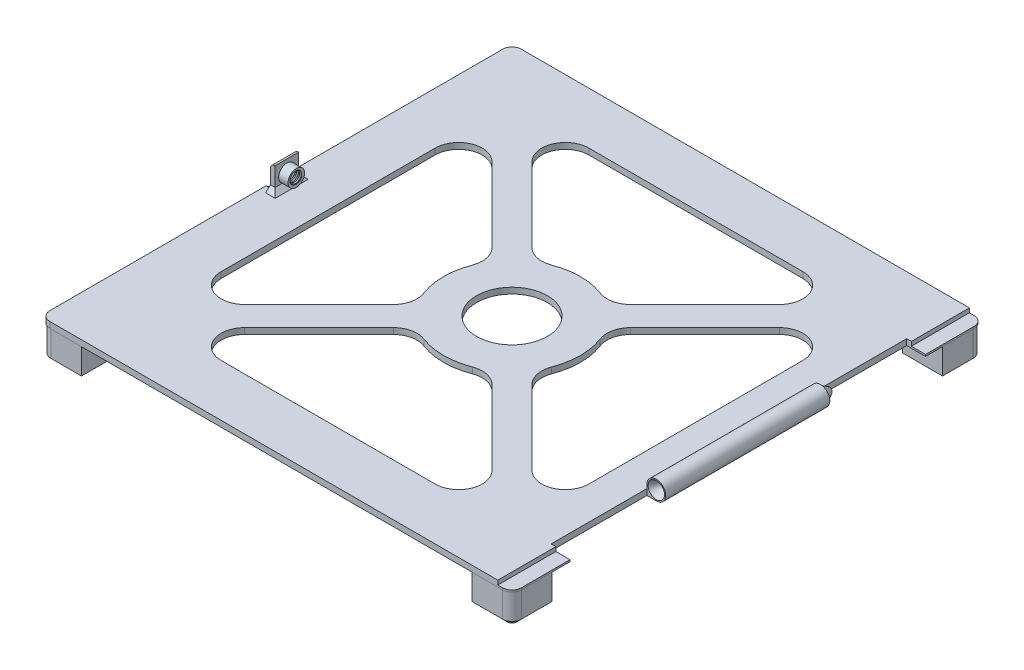
SolidWorks part; units mm, degrees
material "6061 Alloy"
ref_plane "Front Plane" through (0, 0, 0) normal (0, 0, 1) x (1, 0, 0)
ref_plane "Top Plane" through (0, 0, 0) normal (0, 1, 0) x (1, 0, 0)
ref_plane "Right Plane" through (0, 0, 0) normal (1, 0, 0) x (0, 0, -1)
sketch "X-Axis" plane through (0, 0, 0) normal (0, 1, 0) x (1, 0, 0)
  line L2 (-10, 0) -> (10, 0)
  point P3 (0, 0)
  dimension "D1" = 20
sketch "Y-Axis" plane through (0, 0, 0) normal (0, 1, 0) x (1, 0, 0)
  line L0 (0, -10) -> (0, 10)
  dimension "D1" = 20
sketch "Z-Axis" plane through (0, 0, 0) normal (1, 0, 0) x (0, 0, -1)
  line L0 (0, 10) -> (0, -10)
  line L1 (0, 55) -> (0, -55) construction
  point P5 (0, 0)
  dimension "D1" = 20
ref_axis "Axis1" through (0, 0, 0) along (0, 1, 0)
sketch "Sketch1" plane through (0, 0, 0) normal (0, 1, 0) x (1, 0, 0)
  line L0 (-10.4535, 14.6961) -> (-26.2218, 30.4645)
  line L1 (-46, -46) -> (46, -46)
  line L2 (-46, -46) -> (-46, 46)
  line L3 (-46, 46) -> (46, 46)
  line L4 (46, -46) -> (46, 46)
  line L5 (-46, -46) -> (46, 46) construction
  line L6 (-46, 46) -> (46, -46) construction
  line L7 (-22.6863, 39) -> (22.6863, 39)
  line L8 (26.2218, 30.4645) -> (10.4535, 14.6961)
  line L9 (30.4645, -26.2218) -> (14.6961, -10.4535)
  line L10 (14.6961, 10.4535) -> (30.4645, 26.2218)
  line L11 (39, 22.6863) -> (39, -22.6863)
  line L12 (-26.2218, -30.4645) -> (-10.4535, -14.6961)
  line L13 (10.4535, -14.6961) -> (26.2218, -30.4645)
  line L14 (22.6863, -39) -> (-22.6863, -39)
  line L15 (-30.4645, 26.2218) -> (-14.6961, 10.4535)
  line L16 (-14.6961, -10.4535) -> (-30.4645, -26.2218)
  line L17 (-39, -22.6863) -> (-39, 22.6863)
  circle A0 centre (0, 0) radius 7.5
  arc A1 (-5.1441, 13.5569) -> (5.1441, 13.5569) centre (0, 0) cw
  arc A2 (-5.1441, 13.5569) -> (-10.4535, 14.6961) centre (-6.9179, 18.2316) cw
  arc A3 (5.1441, 13.5569) -> (10.4535, 14.6961) centre (6.9179, 18.2316) ccw
  arc A4 (22.6863, 39) -> (26.2218, 30.4645) centre (22.6863, 34) cw
  arc A5 (-26.2218, 30.4645) -> (-22.6863, 39) centre (-22.6863, 34) cw
  arc A6 (13.5569, -5.1441) -> (14.6961, -10.4535) centre (18.2316, -6.9179) ccw
  arc A7 (13.5569, 5.1441) -> (13.5569, -5.1441) centre (0, 0) cw
  arc A8 (13.5569, 5.1441) -> (14.6961, 10.4535) centre (18.2316, 6.9179) cw
  arc A9 (30.4645, 26.2218) -> (39, 22.6863) centre (34, 22.6863) cw
  arc A10 (39, -22.6863) -> (30.4645, -26.2218) centre (34, -22.6863) cw
  arc A11 (-5.1441, -13.5569) -> (-10.4535, -14.6961) centre (-6.9179, -18.2316) ccw
  arc A12 (5.1441, -13.5569) -> (-5.1441, -13.5569) centre (0, 0) cw
  arc A13 (5.1441, -13.5569) -> (10.4535, -14.6961) centre (6.9179, -18.2316) cw
  arc A14 (26.2218, -30.4645) -> (22.6863, -39) centre (22.6863, -34) cw
  arc A15 (-22.6863, -39) -> (-26.2218, -30.4645) centre (-22.6863, -34) cw
  arc A16 (-13.5569, 5.1441) -> (-14.6961, 10.4535) centre (-18.2316, 6.9179) ccw
  arc A17 (-13.5569, -5.1441) -> (-13.5569, 5.1441) centre (0, 0) cw
  arc A18 (-13.5569, -5.1441) -> (-14.6961, -10.4535) centre (-18.2316, -6.9179) cw
  arc A19 (-30.4645, -26.2218) -> (-39, -22.6863) centre (-34, -22.6863) cw
  arc A20 (-39, 22.6863) -> (-30.4645, 26.2218) centre (-34, 22.6863) cw
  point P0 (0, 0)
  point P59 (0, 0)
  dimension "D3" = 15
  dimension "D6" = 7
  dimension "D8" = 5
  dimension "D1" = 92
  dimension "D2" = 92
  dimension "D4" = 6
  dimension "D5" = 6
  dimension "D7" = 7
  dimension "D9" = 4
extrude "Boss-Extrude1" add sketch "Sketch1" along normal blind 1.27
sketch "Sketch6" plane through (0, 0, 0) normal (0, 0, 1) x (1, 0, 0)
  line L0 (46, 2) -> (46, 0)
  line L1 (46, 0) -> (48, 0)
  line L2 (0, 0) -> (0, 69.0457) construction
  arc A0 (46, 2) -> (48, 0) centre (48, 2) cw
  dimension "D1" = 50
extrude "Boss-Extrude3" add sketch "Sketch6" along normal mid plane 34.8
sketch "Sketch7" plane through (0, 0, 17.4) normal (0, 0, 1) x (1, 0, 0)
  circle A0 centre (48, 2) radius 1.75
  dimension "D1" = 3.5
extrude "Cut-Extrude2" cut sketch "Sketch7" against normal blind 2 draft 30
sketch "Sketch8" plane through (0, 0, -17.4) normal (0, 0, -1) x (-1, 0, 0)
  circle A0 centre (-48, 2) radius 1.7
  dimension "D1" = 3.4
extrude "Boss-Extrude4" add sketch "Sketch8" along normal blind 1.9 draft 30
sketch "Sketch16" plane through (0, 0, 0) normal (0, -1, 0) x (1, 0, 0)
  line L1 (-50, 50) -> (-37.7, 50)
  line L2 (-50, 50) -> (-50, 37.7)
  line L3 (-50, 37.7) -> (-37.7, 37.7)
  line L4 (-37.7, 50) -> (-37.7, 37.7)
  dimension "D1" = 50
  dimension "D2" = 50
  dimension "D3" = 37.7
extrude "Boss-Extrude6" add sketch "Sketch16" against normal up to surface (1.27 mm away) up to face at (0, 1.27, 24.6467)
pattern_circular "CirPattern3" count 4 over 360 about axis through (0, 0, 0) along (0, 1, 0) of "Boss-Extrude6"
fillet "Fillet1" radius 2 4 edges at (-50, 0.635, -50) (50, 0.635, -50) (50, 0.635, 50) (-50, 0.635, 50)
sketch "Sketch10" plane through (0, 0, 0) normal (0, -1, 0) x (1, 0, 0)
  line L1 (-47.9, 49.9) -> (-41.4, 49.9)
  line L2 (-49.9, 47.9) -> (-49.9, 41.4)
  line L3 (-49.9, 41.4) -> (-41.4, 41.4)
  line L4 (-41.4, 49.9) -> (-41.4, 41.4)
  line L6 (-37.7, 50) -> (-48, 50) construction
  line L7 (-50, 48) -> (-50, 37.7) construction
  arc A0 (-47.9, 49.9) -> (-49.9, 47.9) centre (-47.9, 47.9) ccw
  dimension "D4" = 2
  dimension "D1" = 0.1
  dimension "D2" = 0.1
  dimension "D3" = 8.5
extrude "Boss-Extrude5" add sketch "Sketch10" along normal blind 6.5
chamfer "Chamfer1" distance 1 angle 45 5 edges at (-45.65, -6.5, 41.4) (-49.9, -6.5, 44.65) (-49.3142, -6.5, 49.3142) (-44.65, -6.5, 49.9) (-41.4, -6.5, 45.65)
sketch "Sketch17" plane through (0, 0, 0) normal (0, -1, 0) x (1, 0, 0)
  line L1 (-37.7, 50) -> (37.7, 50)
  line L2 (-37.7, 50) -> (-37.7, 46)
  line L3 (-37.7, 46) -> (37.7, 46)
  line L4 (37.7, 50) -> (37.7, 46)
  line L5 (-50, 37.7) -> (-46, 37.7)
  line L6 (-50, 37.7) -> (-50, -37.7)
  line L7 (-50, -37.7) -> (-46, -37.7)
  line L8 (-46, 37.7) -> (-46, -37.7)
  line L9 (-37.7, -46) -> (37.7, -46)
  line L10 (-37.7, -46) -> (-37.7, -50)
  line L11 (-37.7, -50) -> (37.7, -50)
  line L12 (37.7, -46) -> (37.7, -50)
extrude "Boss-Extrude7" add sketch "Sketch17" against normal up to surface (1.27 mm away) up to face at (3.5385, 1.27, 0)
pattern_circular "CirPattern2" count 4 over 360 about axis through (0, 0, 0) along (0, 1, 0) of "Boss-Extrude5", "Chamfer1"
sketch "Sketch18" plane through (0, 1.27, 0) normal (0, 1, 0) x (1, 0, 0)
  line L0 (50, 37.7) -> (50, 48) construction
  line L1 (52.2101, 54.3805) -> (47, 54.3805)
  line L2 (52.2101, 54.3805) -> (52.2101, 34.4518)
  line L3 (52.2101, 34.4518) -> (47, 34.4518)
  line L4 (47, 54.3805) -> (47, 34.4518)
  line L5 (52.9916, -51.2544) -> (47, -51.2544)
  line L6 (52.9916, -51.2544) -> (52.9916, -32.3678)
  line L7 (52.9916, -32.3678) -> (47, -32.3678)
  line L8 (47, -51.2544) -> (47, -32.3678)
  dimension "D1" = 3
extrude "Cut-Extrude3" cut sketch "Sketch18" against normal blind 0.9
sketch "Sketch19" plane through (0, 1.27, 0) normal (0, 1, 0) x (1, 0, 0)
  line L1 (-48.73, 2.5) -> (-47.73, 2.5)
  line L2 (-48.73, 2.5) -> (-48.73, -2.5)
  line L3 (-48.73, -2.5) -> (-47.73, -2.5)
  line L4 (-47.73, 2.5) -> (-47.73, -2.5)
  line L5 (-50, 48) -> (-50, -48) construction
  point P6 (-47.73, 0)
  dimension "D1" = 5
  dimension "D2" = 1
  dimension "D3" = 1.27
extrude "Boss-Extrude8" add sketch "Sketch19" along normal blind 5
ref_plane "Plane1" through (-50.73, 0, 0) normal (-1, 0, 0) x (0, 0, 1)
sketch "Sketch25" plane through (-47.73, 0, 0) normal (1, 0, 0) x (0, 0, -1)
  line L1 (-17.4, 1.27) -> (17.4, 1.27) construction
  circle A0 centre (0, 3.77) radius 1.75
  dimension "D1" = 3.5
  dimension "D2" = 2.5
extrude "Boss-Extrude9" add sketch "Sketch25" along normal blind 2
hole_wizard "Tap Drill for #4-40 Tap1" positions "Sketch21" profile "Sketch20" hole size "#4-40" standard "ANSI Inch" end condition up to next
sketch "Sketch21" plane through (-48.73, 0, 0) normal (-1, 0, 0) x (0, 0, 1)
  circle A0 centre (0, 3.77) radius 1.75 construction
  point P0 (0, 3.77)
sketch "Sketch20" plane through (-48.73, 3.77, 0) normal (0, 1, 0) x (0, 0, 1)
  line L0 (0, 0) -> (0, 3)
  line L1 (0, 3) -> (1.1303, 3)
  line L2 (1.1303, 3) -> (1.1303, 0)
  line L5 (1.1303, 0) -> (0, 0)
  line L11 (0, -6.35) -> (0, 107.95) construction
  dimension "Thru Hole Dia." = 2.2606
  dimension "Thru Hole Depth" = 3
ref_axis "Axis2" through (-45.73, 3.77, 0) along (-1, 0, 0)
fillet "Fillet2" radius 1 1 edges at (-48.73, 6.27, 0)
chamfer "Chamfer2" distance 1 angle 45 3 edges at (-48.23, 1.27, -2.5) (-47.73, 1.27, 0) (-48.23, 1.27, 2.5)
sketch "Sketch23" plane through (-50.73, 0, 0) normal (-1, 0, 0) x (0, 0, 1)
  circle A0 centre (0, 3.77) radius 1.1303 construction
  circle A1 centre (0, 3.77) radius 1.1303
curve "Helix/Spiral1" pitch 0.635 height 9.525 radius 1.1303 centre (-50.73, 3.77, 0) axis (1, 0, 0) start towards (0, 0, 1)
ref_plane "Plane2" through (-50.73, 3.77, 1.1303) normal (0.0891, -0.996, 0) x (-0.996, -0.0891, 0)
sketch "Sketch24" plane through (-50.73, 3.77, 1.1303) normal (0.0891, -0.996, 0) x (-0.996, -0.0891, 0)
  line L0 (0.0397, -0.2921) -> (-0.0397, -0.2921)
  line L1 (-0.0397, -0.2921) -> (-0.2706, 0.1079)
  line L3 (-0.2706, 0.1079) -> (0.2706, 0.1079)
  line L4 (0.2706, 0.1079) -> (0.0397, -0.2921)
  line L6 (-4.9801, 1.1303) -> (-1.9921, 1.1303) construction
  point P3 (0, 0)
  point P4 (0, -0.2921)
  dimension "D1" = 60
  dimension "D2" = 0.0794
  dimension "D3" = 1.4224
  dimension "D4" = 60
  dimension "D5" = 0.4
sweep "Cut-Sweep3" cut profiles "Sketch24" path "Helix/Spiral1"
sketch "Sketch26" plane through (-50, 0, 0) normal (-1, 0, 0) x (0, 0, 1)
  circle A0 centre (0, 3.77) radius 3.302
  circle A1 centre (0, 3.77) radius 1.75 construction
  dimension "D1" = 6.604
extrude "Cut-Extrude4" cut sketch "Sketch26" against normal blind 1
